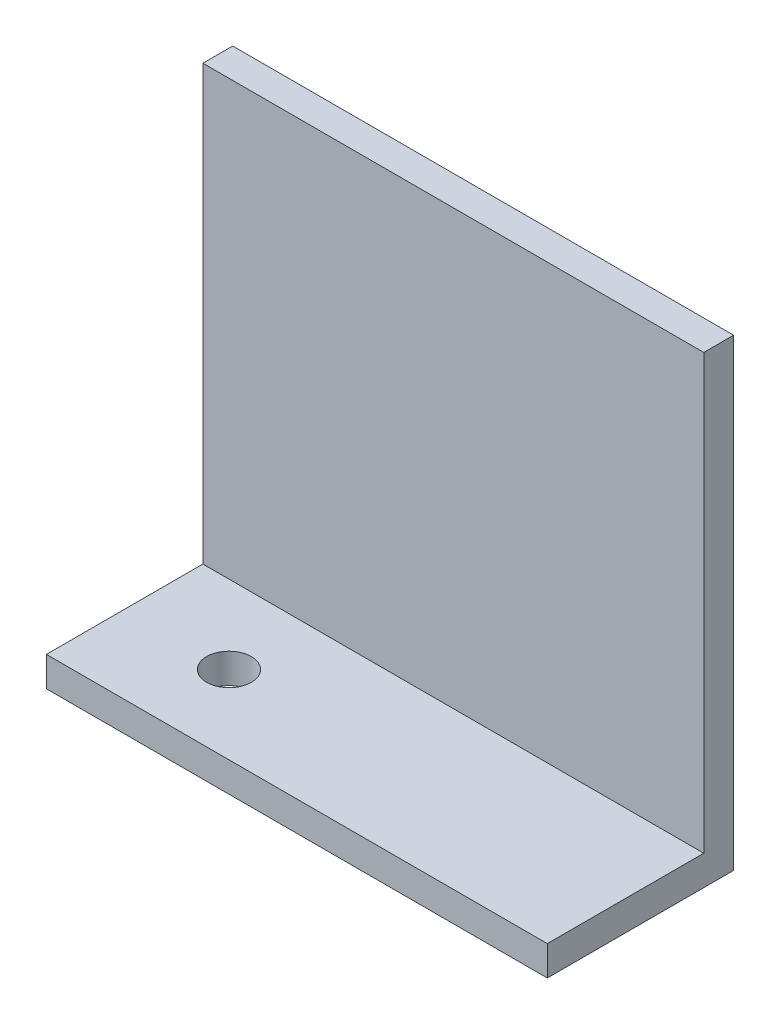
SolidWorks part; units mm, degrees
ref_plane "Front Plane" through (0, 0, 0) normal (0, 0, 1) x (1, 0, 0)
ref_plane "Top Plane" through (0, 0, 0) normal (0, 1, 0) x (1, 0, 0)
ref_plane "Right Plane" through (0, 0, 0) normal (1, 0, 0) x (0, 0, -1)
sketch "Sketch1" plane through (0, 0, 0) normal (0, 1, 0) x (1, 0, 0)
  line L1 (0, 0) -> (33.6093, 0)
  line L2 (0, 0) -> (0, 12.5)
  line L3 (0, 12.5) -> (33.6093, 12.5)
  line L4 (33.6093, 0) -> (33.6093, 12.5)
  dimension "D1" = 12.5
extrude "Boss-Extrude1" add sketch "Sketch1" along normal blind 2
sketch "Sketch2" plane through (0, 0, -12.5) normal (0, 0, -1) x (-1, 0, 0)
  line L1 (-33.6093, 2) -> (0, 2)
  line L2 (-33.6093, 2) -> (-33.6093, 31.1024)
  line L3 (-33.6093, 31.1024) -> (0, 31.1024)
  line L4 (0, 2) -> (0, 31.1024)
extrude "Boss-Extrude2" add sketch "Sketch2" against normal blind 2
sketch "Sketch3" plane through (0, 2, 0) normal (0, 1, 0) x (1, 0, 0)
  line L0 (0, 5.25) -> (33.6093, 5.25) construction
  line L1 (0, 10.5) -> (0, 0) construction
  line L2 (33.6093, 0) -> (33.6093, 10.5) construction
  circle A0 centre (7, 5.25) radius 1.5
  dimension "D1" = 3
  dimension "D2" = 5.5
extrude "Cut-Extrude1" cut sketch "Sketch3" against normal blind 2 contours A0
sketch "Sketch4" plane through (0, 0, -12.5) normal (0, 0, -1) x (-1, 0, 0)
  line L1 (0, 31.1024) -> (0, 0) construction
  circle A0 centre (-11, 18.5943) radius 8
  point P2 (-9.8668, 15.3728)
  point P3 (0, 0)
  point P4 (-10.1809, 18.5943)
  dimension "D1" = 16
  dimension "D2" = 3
